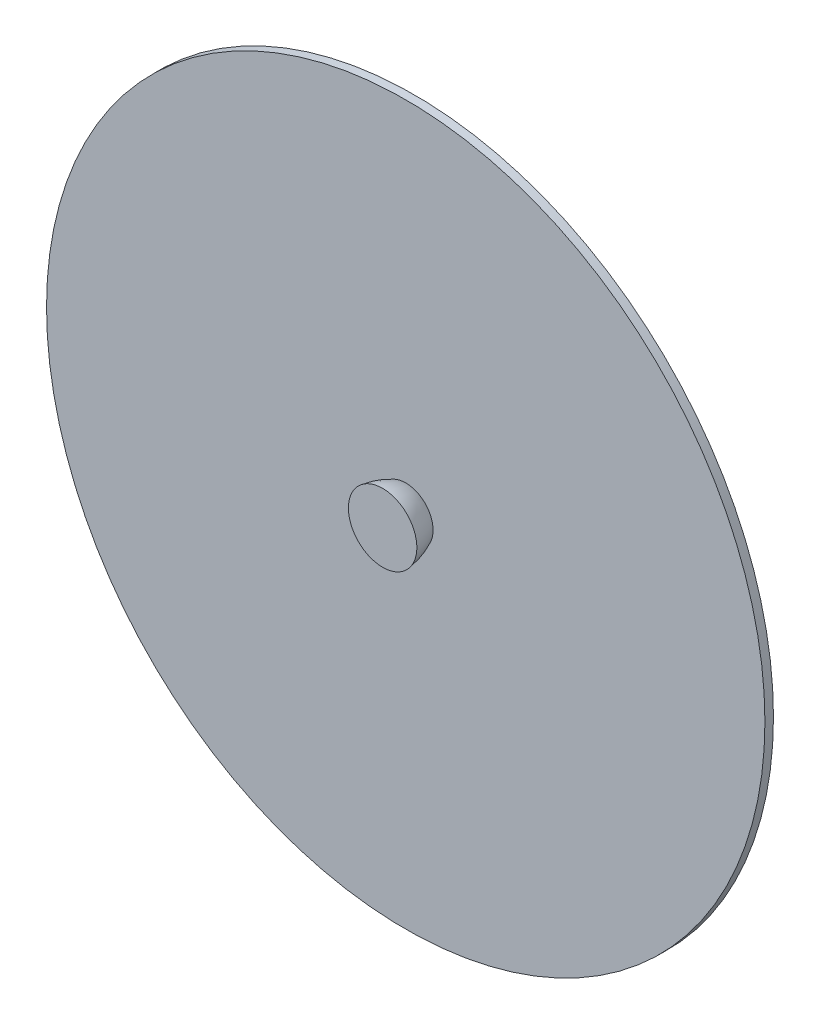
SolidWorks part; units mm, degrees
ref_plane "Plano frontal" through (0, 0, 0) normal (0, 0, 1) x (1, 0, 0)
ref_plane "Plano superior" through (0, 0, 0) normal (0, 1, 0) x (1, 0, 0)
ref_plane "Plano direito" through (0, 0, 0) normal (1, 0, 0) x (0, 0, -1)
sketch "Esboço1" plane through (0, 0, 0) normal (0, 1, 0) x (1, 0, 0)
  line L0 (0, 1000) -> (0, -1000) construction
  line L1 (-200, 700) -> (0, 700)
  line L2 (-130, 885) -> (-2100, 885)
  line L3 (-2100, 885) -> (-2100, 835)
  line L4 (-2100, 835) -> (-160.0074, 835)
  line L6 (0, 1000) -> (0, 700)
  spline S0 degree 2 poles (0, 1000) (-81.0253, 953.5611) (-130, 885) knots 0 0 0 0.467371 0.467371 0.467371
  spline S1 degree 2 poles (-160.0074, 835) (-190.1127, 774.4775) (-200, 700) knots 0.628797 0.628797 0.628797 1 1 1
  dimension "D1" = 2000
  dimension "D2" = 200
  dimension "D3" = 300
  dimension "D4" = 185
  dimension "D5" = 130
  dimension "D6" = 50
  dimension "D7" = 2100
revolve "Revolução1" add sketch "Esboço1" angle 360 about L6
